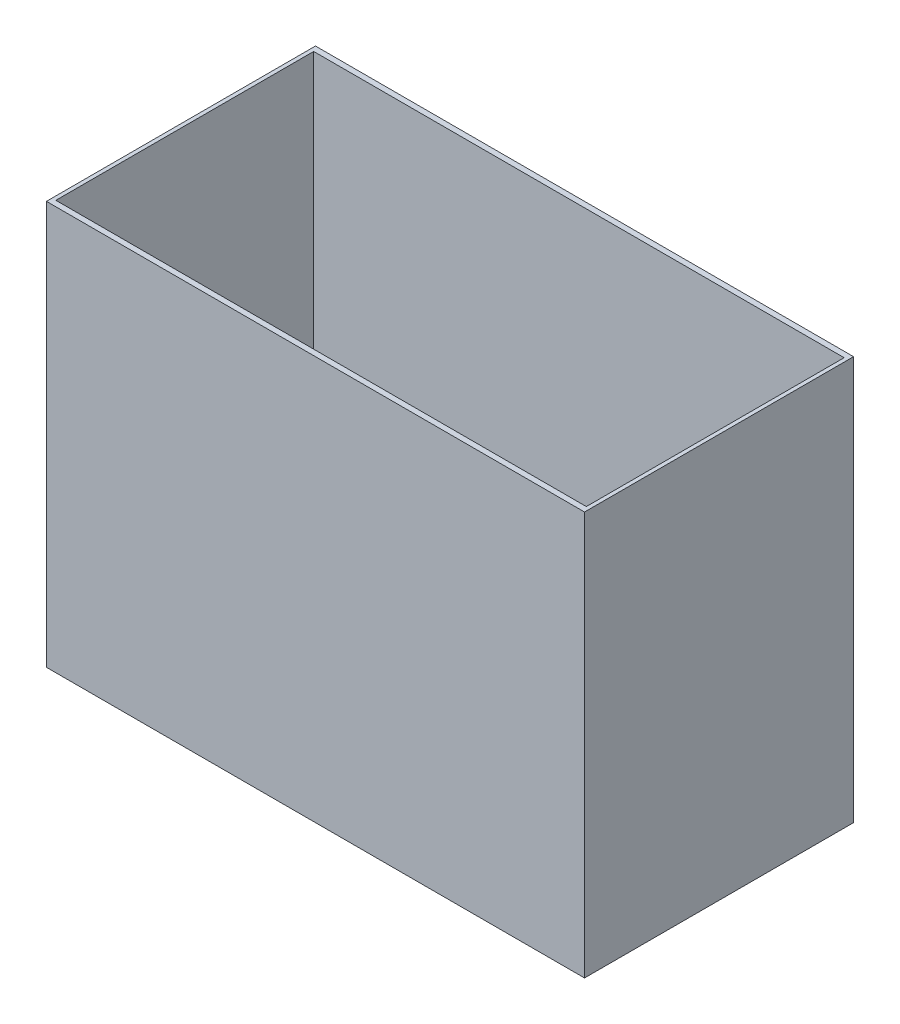
SolidWorks part; units mm, degrees
ref_plane "Front Plane" through (0, 0, 0) normal (0, 0, 1) x (1, 0, 0)
ref_plane "Top Plane" through (0, 0, 0) normal (0, 1, 0) x (1, 0, 0)
ref_plane "Right Plane" through (0, 0, 0) normal (1, 0, 0) x (0, 0, -1)
other "Bounding Box"
ref_plane "Default Plane" through (-292.1, 0, -139.7) normal (0, 1, 0) x (1, 0, 0)
sketch "Sketch1" plane through (0, 0, 0) normal (0, 1, 0) x (1, 0, 0)
  line L0 (-292.1, 0) -> (292.1, 0) construction
  line L1 (-292.1, 139.7) -> (292.1, 139.7)
  line L2 (-292.1, 139.7) -> (-292.1, -139.7)
  line L3 (-292.1, -139.7) -> (292.1, -139.7)
  line L4 (292.1, 139.7) -> (292.1, -139.7)
  line L5 (0, 139.7) -> (0, -139.7) construction
  point P8 (0, 0)
  dimension "D1" = 584.2
  dimension "D2" = 279.4
extrude "Boss-Extrude1" add sketch "Sketch1" along normal blind 12.7
sketch "Sketch2" plane through (0, 12.7, 0) normal (0, 1, 0) x (1, 0, 0)
  line L0 (-245.9259, -63.5) -> (-55.3589, -63.5) construction
  line L1 (-241.3, -120.6497) -> (-152.4, -120.6497)
  line L2 (-241.3, -120.6497) -> (-241.3, -101.5997)
  line L3 (-241.3, -101.5997) -> (-152.4, -101.5997)
  line L4 (-152.4, -120.6497) -> (-152.4, -101.5997)
  line L5 (-241.3, -120.6497) -> (-152.4, -101.5997) construction
  line L6 (-241.3, -101.5997) -> (-152.4, -120.6497) construction
  line L7 (-292.1, 139.7) -> (-292.1, -139.7) construction
  line L8 (-292.1, 0) -> (292.1, 0) construction
  line L9 (292.1, -139.7) -> (292.1, 139.7) construction
  line L10 (0, 0) -> (0, 121.6784) construction
  line L11 (241.3, -101.5997) -> (152.4, -120.6497) construction
  line L12 (241.3, -120.6497) -> (152.4, -101.5997) construction
  line L13 (152.4, -120.6497) -> (152.4, -101.5997)
  line L14 (241.3, -101.5997) -> (152.4, -101.5997)
  line L15 (241.3, -120.6497) -> (241.3, -101.5997)
  line L16 (241.3, -120.6497) -> (152.4, -120.6497)
  point P0 (-196.85, -111.1247)
  point P17 (196.85, -111.1247)
  dimension "D1" = 19.05
  dimension "D2" = 88.9
  dimension "D3" = 38.0997
  dimension "D4" = 50.8
  dimension "D5" = 63.5
extrude "Boss-Extrude2" [suppressed] add sketch "Sketch2" along normal blind 304.8 separate body contours L2 L1 L4 L3
pattern_linear "LPattern1" [suppressed] count 2 spacing 304.8 of bodies 101
pattern_linear "LPattern2" [suppressed] count 2 spacing 215.9 of bodies 101
sketch "Sketch3" plane through (0, 0, 0) normal (0, 1, 0) x (1, 0, 0)
  line L1 (-304.8, -152.4) -> (304.8, -152.4)
  line L2 (-304.8, -152.4) -> (-304.8, 152.4)
  line L3 (-304.8, 152.4) -> (304.8, 152.4)
  line L4 (304.8, -152.4) -> (304.8, 152.4)
  line L5 (-304.8, -152.4) -> (304.8, 152.4) construction
  line L6 (-304.8, 152.4) -> (304.8, -152.4) construction
  line L7 (-300.482, -146.05) -> (300.482, -146.05)
  line L8 (-300.482, -146.05) -> (-300.482, 146.05)
  line L9 (-300.482, 146.05) -> (300.482, 146.05)
  line L10 (300.482, -146.05) -> (300.482, 146.05)
  line L11 (-300.482, -146.05) -> (300.482, 146.05) construction
  line L12 (-300.482, 146.05) -> (300.482, -146.05) construction
  point P0 (0, 0)
  point P6 (0, 0)
  dimension "D1" = 609.6
  dimension "D2" = 304.8
  dimension "D3" = 292.1
  dimension "D4" = 600.964
extrude "Boss-Extrude3" add sketch "Sketch3" along normal blind 457.2 separate body
sketch "Sketch4" plane through (0, 12.7, 0) normal (0, 1, 0) x (1, 0, 0)
  line L0 (292.1, 139.7) -> (-292.1, 139.7) construction
  line L1 (292.1, -139.7) -> (292.1, 139.7) construction
  circle A0 centre (254, 101.6) radius 2.7781
  dimension "D1" = 5.5562
  dimension "D2" = 38.1
  dimension "D3" = 38.1
extrude "Cut-Extrude1" cut sketch "Sketch4" against normal through all
sketch "Sketch6" plane through (0, 0, 0) normal (0, -1, 0) x (1, 0, 0)
  circle A0 centre (254, -101.6) radius 6.35
  circle A1 centre (254, -101.6) radius 2.7781 construction
  point P2 (247.1988, 78.7391)
  dimension "D1" = 12.7
extrude "Cut-Extrude2" cut sketch "Sketch6" against normal blind 2.54
mirror "Mirror1" about plane through (0, 0, 0) normal (0, 0, 1) of "Cut-Extrude2", "Cut-Extrude1"
